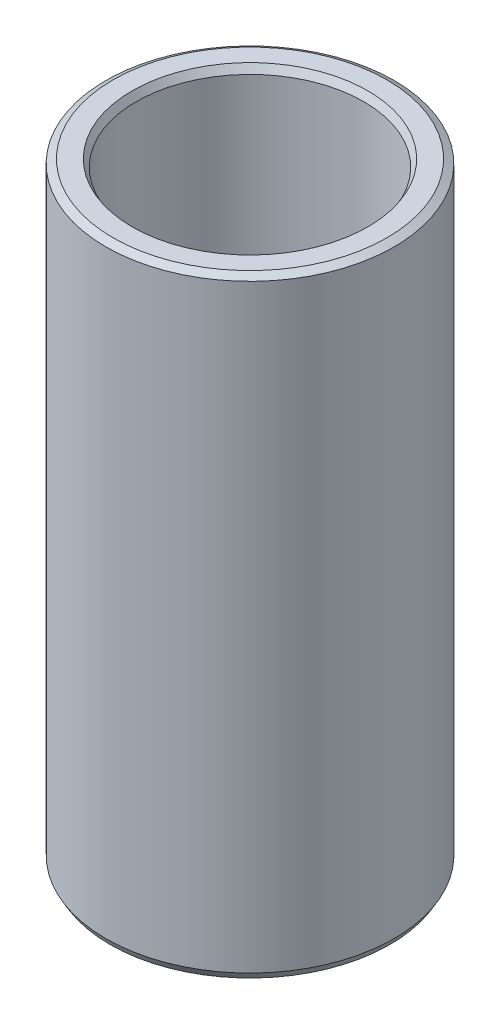
SolidWorks part; units mm, degrees
ref_plane "Front Plane" through (0, 0, 0) normal (0, 0, 1) x (1, 0, 0)
ref_plane "Top Plane" through (0, 0, 0) normal (0, 1, 0) x (1, 0, 0)
ref_plane "Right Plane" through (0, 0, 0) normal (1, 0, 0) x (0, 0, -1)
sketch "Sketch1" plane through (0, 0, 0) normal (0, 1, 0) x (1, 0, 0)
  circle A0 centre (0, 0) radius 50
  dimension "SLEEVE_OD" = 100
extrude "Boss-Extrude1" add sketch "Sketch1" along normal blind 211.7722
sketch "Sketch2" plane through (0, 0, 0) normal (0, 1, 0) x (1, 0, 0)
  circle A0 centre (0, 0) radius 39.4337
  dimension "BORE_D" = 78.8674
extrude "Cut-Extrude1" cut sketch "Sketch2" along normal through all
chamfer "Chamfer1" distance 1.4538 angle 60 4 edges at (0, 211.7722, 39.4337) (0, 0, 39.4337) (0, 0, 50) (0, 211.7722, 50) first distance on face at (0, 211.7722, 39.4337) first distance on face at (0, 0, 39.4337) first distance on face at (0, 211.7722, 50)
